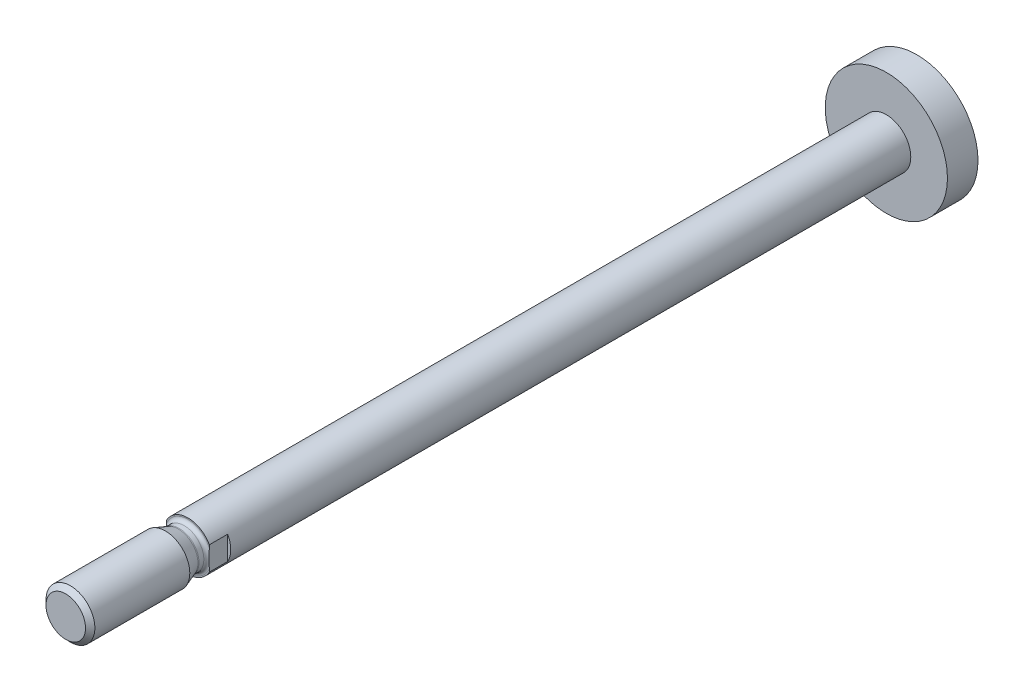
SolidWorks part; units mm, degrees
ref_plane "Front Plane" through (0, 0, 0) normal (0, 0, 1) x (1, 0, 0)
ref_plane "Top Plane" through (0, 0, 0) normal (0, 1, 0) x (1, 0, 0)
ref_plane "Right Plane" through (0, 0, 0) normal (1, 0, 0) x (0, 0, -1)
sketch "Sketch1" plane through (0, 0, 0) normal (1, 0, 0) x (0, 0, -1)
  line L0 (-4, 0) -> (-4, 4)
  line L1 (-4, 4) -> (110.3, 4)
  line L2 (110.3, 4) -> (110.3, 10)
  line L3 (110.3, 10) -> (115.3, 10)
  line L4 (115.3, 10) -> (115.3, 0)
  line L5 (115.3, 0) -> (-4, 0)
  line L6 (115.3, 0) -> (-4, 0) construction
revolve "Revolve1" add sketch "Sketch1" angle 360 about L6 reverse direction yes
sketch "Sketch2" plane through (0, 0, 0) normal (1, 0, 0) x (0, 0, -1)
  line L0 (-24, 0) -> (-24, 3.233)
  line L1 (-24, 3.233) -> (-23.233, 4)
  line L2 (-23.233, 4) -> (-7.698, 4)
  line L3 (-7.698, 4) -> (-5.5994, 3.2362)
  line L4 (-5.3942, 3.2) -> (-4.6, 3.2)
  line L5 (-4, 3.8) -> (-4, 4)
  line L6 (-4, 4) -> (-3, 4)
  line L7 (-3, 4) -> (-3, 0)
  line L8 (-3, 0) -> (-24, 0)
  line L9 (-3, 0) -> (-24, 0) construction
  arc A0 (-5.5994, 3.2362) -> (-5.3942, 3.2) centre (-5.3942, 3.8) ccw
  arc A1 (-4.6, 3.2) -> (-4, 3.8) centre (-4.6, 3.8) ccw
revolve "Revolve2" add sketch "Sketch2" angle 360 about L9 reverse direction yes
cosmetic thread "Cosmetic Thread1" parameters "D1"=16.302, "D2"=6.466
ref_plane "Plane1" through (0, 0, 4) normal (0, 0, 1) x (1, 0, 0)
ref_plane "Plane2" through (0, 0, 1) normal (0, 0, 1) x (1, 0, 0)
sketch "Sketch3" plane through (0, 0, 1) normal (0, 0, 1) x (1, 0, 0)
  line L0 (-7, 14) -> (-7, -7)
  line L1 (-7, -7) -> (-3.5, -7)
  line L2 (-3.5, -7) -> (-3.5, 7)
  line L3 (-3.5, 7) -> (3.5, 7)
  line L4 (3.5, 7) -> (3.5, -7)
  line L5 (3.5, -7) -> (7, -7)
  line L6 (7, -7) -> (7, 14)
  line L7 (7, 14) -> (-7, 14)
extrude "Cut-Extrude1" cut sketch "Sketch3" along normal blind 4
ref_plane "Plane3" through (0, 0, -232) normal (0, 0, 1) x (1, 0, 0)
ref_plane "Plane4" through (0, 0, 20) normal (0, 0, 1) x (1, 0, 0)
ref_plane "Plane5" through (0, 0, 12) normal (0, 0, 1) x (1, 0, 0)
ref_plane "FDT_KSAUFSATZ XY" through (0, 0, 12) normal (0, 0, 1) x (1, 0, 0)
ref_plane "FDT_KSAUFSATZ XZ" through (0, 0, 0) normal (0, 1, 0) x (1, 0, 0)
ref_plane "FDT_KSAUFSATZ YZ" through (0, 0, 0) normal (-1, 0, 0) x (0, 0, 1)
ref_axis "FDT_KSAUFSATZ X" through (80.9, 0, 12) along (-1, 0, 0)
ref_axis "FDT_KSAUFSATZ Y" through (0, 50, 12) along (0, -1, 0)
ref_axis "FDT_KSAUFSATZ Z" through (0, 0, 80.9) along (0, 0, -1)
sketch3d "FDT_KSAUFSATZ"
  point P0 (0, 0, 12)
ref_plane "FDT_NUT XY" through (0, 0, 12) normal (0, 0, 1) x (1, 0, 0)
ref_plane "FDT_NUT XZ" through (0, 0, 0) normal (0, 1, 0) x (1, 0, 0)
ref_plane "FDT_NUT YZ" through (0, 0, 0) normal (-1, 0, 0) x (0, 0, 1)
ref_axis "FDT_NUT X" through (80.9, 0, 12) along (-1, 0, 0)
ref_axis "FDT_NUT Y" through (0, 50, 12) along (0, -1, 0)
ref_axis "FDT_NUT Z" through (0, 0, 80.9) along (0, 0, -1)
sketch3d "FDT_NUT"
  point P0 (0, 0, 12)
ref_plane "KS XY" through (0, 0, 0) normal (0, 0, -1) x (-1, 0, 0)
ref_plane "KS XZ" through (0, 0, 0) normal (0, 1, 0) x (1, 0, 0)
ref_plane "KS YZ" through (0, 0, 0) normal (1, 0, 0) x (0, 0, -1)
ref_axis "KS X" through (-80.9, 0, 0) along (1, 0, 0)
ref_axis "KS Y" through (0, 50, 0) along (0, -1, 0)
ref_axis "KS Z" through (0, 0, -80.9) along (0, 0, 1)
sketch3d "KS"
  point P0 (0, 0, 0)
ref_plane "NUT1 XY" through (0, 0, 20) normal (0, 0, 1) x (1, 0, 0)
ref_plane "NUT1 XZ" through (0, 0, 0) normal (0, -1, 0) x (-1, 0, 0)
ref_plane "NUT1 YZ" through (0, 0, 0) normal (1, 0, 0) x (0, 0, -1)
ref_axis "NUT1 X" through (-80.9, 0, 20) along (1, 0, 0)
ref_axis "NUT1 Y" through (0, -50, 20) along (0, 1, 0)
ref_axis "NUT1 Z" through (0, 0, 80.9) along (0, 0, -1)
sketch3d "NUT1"
  point P0 (0, 0, 20)
